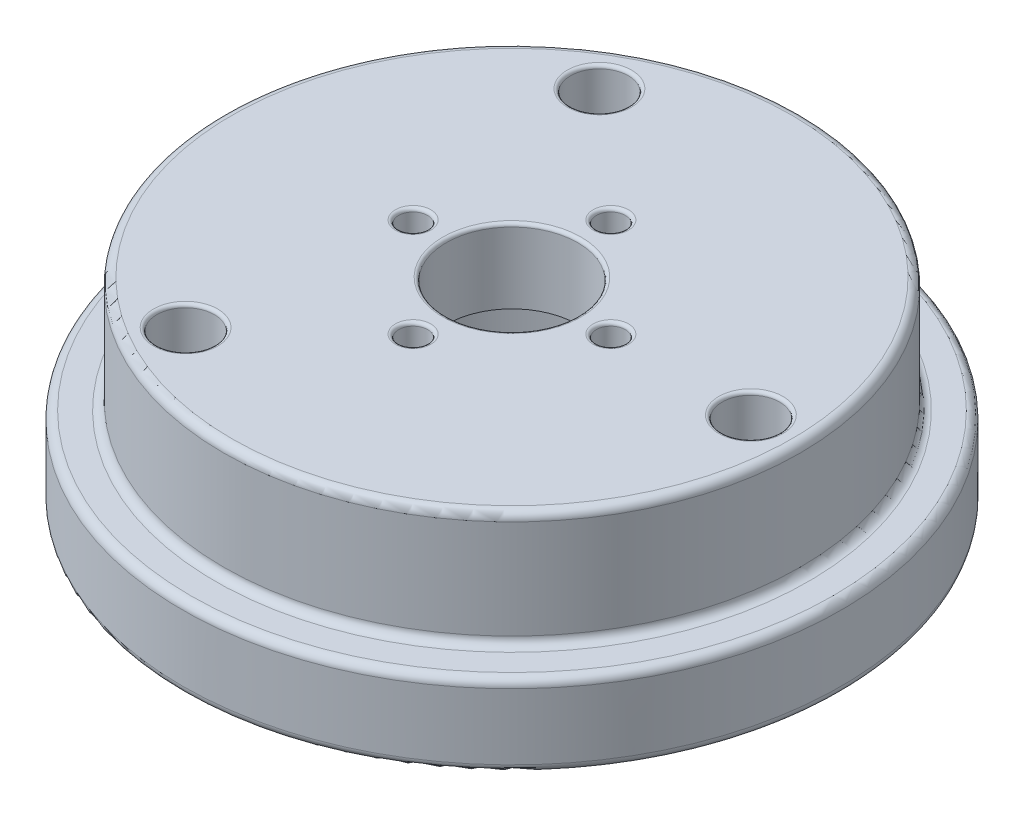
SolidWorks part; units mm, degrees
ref_plane "Front Plane" through (0, 0, 0) normal (0, 0, 1) x (1, 0, 0)
ref_plane "Top Plane" through (0, 0, 0) normal (0, 1, 0) x (1, 0, 0)
ref_plane "Right Plane" through (0, 0, 0) normal (1, 0, 0) x (0, 0, -1)
sketch "Sketch1" plane through (0, 0, 0) normal (0, 0, 1) x (1, 0, 0)
  line L0 (0, 0) -> (0, 9431.4312) construction
  line L1 (0, 0) -> (-9431.4312, 0) construction
  line L2 (0, 0) -> (-20, 0)
  line L3 (-20, 0) -> (-20, 5)
  line L4 (-20, 5) -> (-17.5, 5)
  line L5 (-17.5, 5) -> (-17.5, 12)
  line L6 (-17.5, 12) -> (0, 12)
  line L7 (0, 12) -> (0, 0)
  dimension "D1" = 20
  dimension "D2" = 5
  dimension "D3" = 12
  dimension "D4" = 17.5
revolve "Revolve1" add sketch "Sketch1" angle 360 about L0
sketch "Sketch2" plane through (0, 0, 0) normal (0, -1, 0) x (1, 0, 0)
  circle A0 centre (0, 0) radius 10
  circle A1 centre (14.5, 0) radius 1.75
  circle A2 centre (-7.25, -12.5574) radius 1.75
  circle A3 centre (-7.25, 12.5574) radius 1.75
  circle A4 centre (0, 0) radius 4
  circle A5 centre (6, 0) radius 0.875
  circle A6 centre (0, -6) radius 0.875
  circle A7 centre (-6, 0) radius 0.875
  circle A8 centre (0, 6) radius 0.875
  dimension "D1" = 20
  dimension "D3" = 3.5
  dimension "D5" = 8
  dimension "D6" = 1.75
  dimension "D2" = 14.5
  dimension "D7" = 6
  dimension "D9" = 14.5
  dimension "D4" = 3
  dimension "D8" = 4
extrude "Cut-Extrude1" cut sketch "Sketch2" against normal through all contours A2 | A4 | A1 | A3 | A7 | A6 | A5 | A8 region at (14.5, 0, 0) region at (-7.25, 0, -12.5574) region at (-7.25, 0, 12.5574) region at (0, 0, 0) region at (6, 0, 0) region at (0, 0, -6) region at (-6, 0, 0) region at (0, 0, 6)
extrude "Cut-Extrude2" cut sketch "Sketch2<3>" against normal blind 7.5 contours A0 A8 A7 A6 A5 A4 region at (-9.7172, 0, 0)
sketch "Sketch2<3>" plane through (0, 0, 0) normal (0, -1, 0) x (1, 0, 0) same geometry as "Sketch2"
fillet "Fillet1" radius 0.5 4 edges at (0, 0, -20) (0, 5, -20) (0, 5, -17.5) (0, 12, -17.5)
fillet "Fillet2" radius 0.2 8 edges at (0, 12, -4) (14.5, 12, -1.75) (-7.25, 12, 10.8074) (-6, 12, -0.875) (0, 12, -6.875) (6, 12, -0.875) (0, 12, 5.125) (-7.25, 12, -14.3074)
fillet "Fillet3" radius 0.1 4 edges at (-7.25, 0, -14.3074) (14.5, 0, -1.75) (-7.25, 0, 10.8074) (0, 0, -10)
